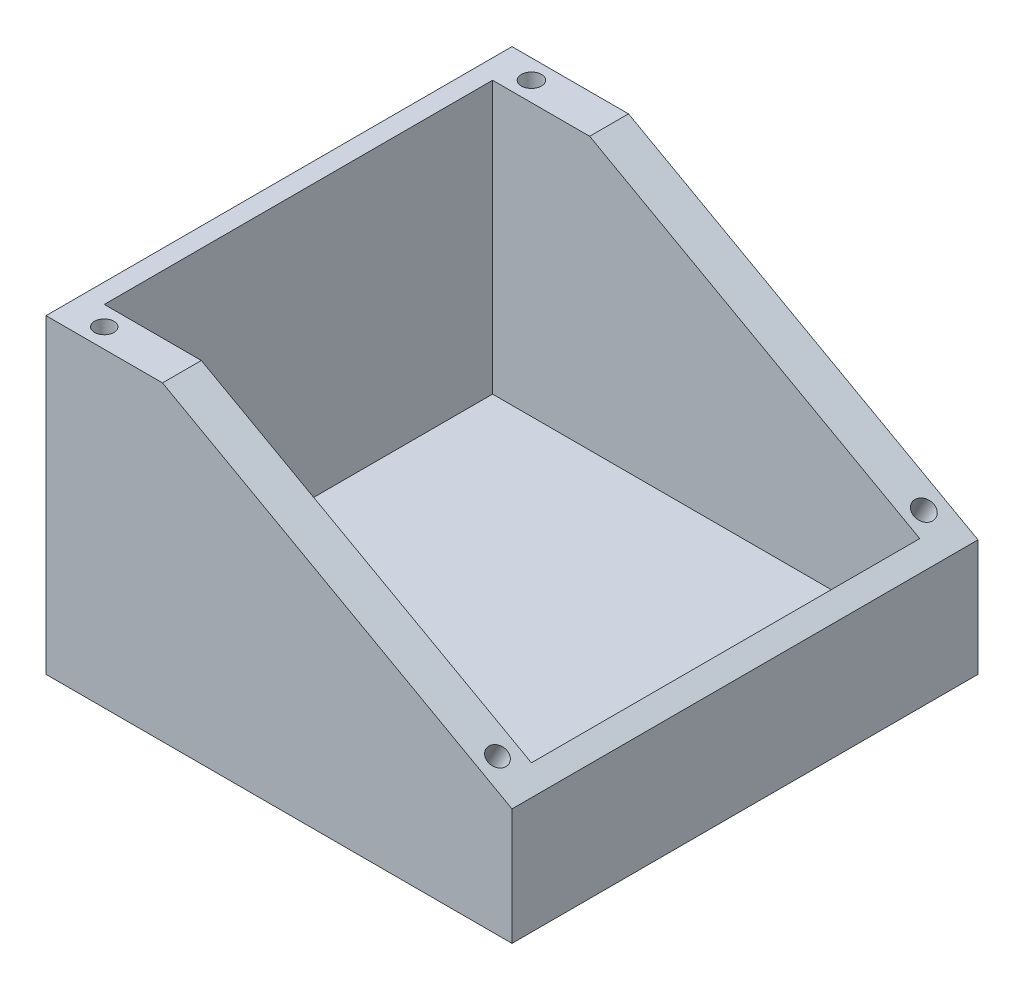
SolidWorks part; units mm, degrees
ref_plane "Front Plane" through (0, 0, 0) normal (0, 0, 1) x (1, 0, 0)
ref_plane "Top Plane" through (0, 0, 0) normal (0, 1, 0) x (1, 0, 0)
ref_plane "Right Plane" through (0, 0, 0) normal (1, 0, 0) x (0, 0, -1)
sketch "Sketch1" plane through (0, 0, 0) normal (0, 0, 1) x (1, 0, 0)
  line L0 (0, 0) -> (0, 101.6)
  line L1 (0, 101.6) -> (152.4, 101.6)
  line L2 (152.4, 101.6) -> (152.4, 0)
  line L3 (152.4, 0) -> (0, 0)
  dimension "D1" = 101.6
  dimension "D2" = 152.4
extrude "Boss-Extrude1" add sketch "Sketch1" along normal blind 152.4
sketch "Sketch6" plane through (0, 0, 152.4) normal (0, 0, 1) x (1, 0, 0)
  line L0 (38.1, 101.6) -> (152.4, 101.6)
  line L1 (152.4, 101.6) -> (0, 101.6) construction
  line L2 (152.4, 101.6) -> (152.4, 38.1)
  line L3 (152.4, 0) -> (152.4, 101.6) construction
  line L4 (152.4, 38.1) -> (38.1, 101.6)
  line L5 (104.4367, 101.6) -> (104.5902, 101.6)
  line M5 (152.4, 0) -> (152.4, 101.6)
  line M6 (152.4, 101.6) -> (0, 101.6)
  dimension "D1" = 63.5
  dimension "D2" = 114.3
extrude "Cut-Extrude2" cut sketch "Sketch6" against normal blind 152.4 contours L4 L0 M5 M6 region at (114.3, 80.4333, 152.4)
sketch "Sketch7" plane through (0, 101.6, 0) normal (0, 1, 0) x (1, 0, 0)
  line L0 (6.35, -12.7) -> (6.35, -139.7)
  line L1 (6.35, -139.7) -> (146.05, -139.7)
  line L2 (146.05, -139.7) -> (146.05, -12.7)
  line L3 (146.05, -12.7) -> (6.35, -12.7)
  line L4 (38.1, 0) -> (0, 0) construction
  line L5 (0, -152.4) -> (0, 0) construction
  line L6 (152.4, -152.4) -> (38.1, -152.4) construction
  line L7 (152.4, 0) -> (152.4, -152.4) construction
  dimension "D1" = 12.7
  dimension "D2" = 6.35
  dimension "D3" = 12.7
  dimension "D4" = 6.35
extrude "Cut-Extrude3" cut sketch "Sketch7" against normal blind 88.9
sketch "Sketch8" plane through (0, 101.6, 0) normal (0, 1, 0) x (1, 0, 0)
  line L0 (38.1, -152.4) -> (0, -152.4) construction
  line L1 (0, -152.4) -> (0, 0) construction
  line L2 (38.1, 0) -> (0, 0) construction
  circle A0 centre (12.7, -146.05) radius 3.175
  circle A1 centre (12.7, -6.35) radius 3.302
  point P10 (0, 0)
  point P12 (0, -4.3699)
  dimension "D1" = 6.35
  dimension "D2" = 6.604
  dimension "D4" = 12.7
  dimension "D3" = 6.35
  dimension "D5" = 6.35
  dimension "D6" = 12.7
extrude "Cut-Extrude4" cut sketch "Sketch8" against normal blind 12.7
sketch "Sketch9" plane through (52.1179, 93.8123, 0) normal (0.4856, 0.8742, 0) x (0.8742, -0.4856, 0)
  line L0 (114.7186, -152.4) -> (-16.0359, -152.4) construction
  line L1 (114.7186, 0) -> (-16.0359, 0) construction
  line L2 (114.7186, 0) -> (114.7186, -152.4) construction
  circle A0 centre (102.0186, -146.05) radius 3.175
  circle A1 centre (102.0186, -6.604) radius 3.302
  dimension "D1" = 6.604
  dimension "D2" = 6.35
  dimension "D3" = 6.35
  dimension "D4" = 6.604
  dimension "D5" = 12.7
  dimension "D6" = 12.7
extrude "Cut-Extrude5" cut sketch "Sketch9" against normal blind 12.7
